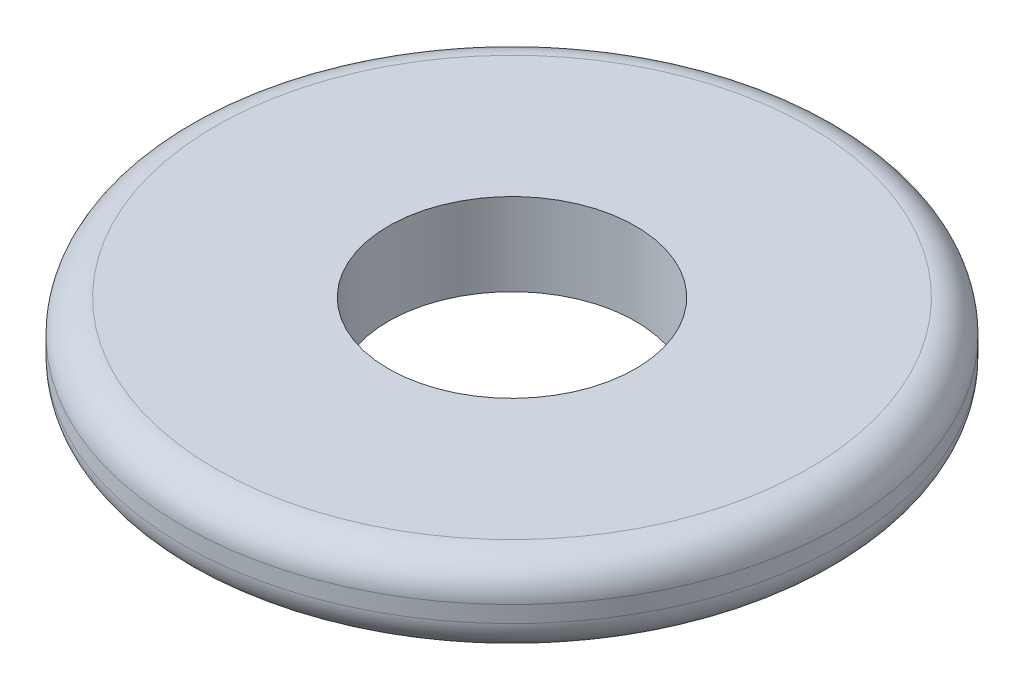
SolidWorks part; units mm, degrees
ref_plane "Front Plane" through (0, 0, 0) normal (0, 0, 1) x (1, 0, 0)
ref_plane "Top Plane" through (0, 0, 0) normal (0, 1, 0) x (1, 0, 0)
ref_plane "Right Plane" through (0, 0, 0) normal (1, 0, 0) x (0, 0, -1)
sketch "Sketch1" plane through (0, 0, 0) normal (0, 1, 0) x (1, 0, 0)
  circle A0 centre (0, 0) radius 25.4
  circle A2 centre (0, 0) radius 9.525
  dimension "D1" = 50.8
  dimension "D2" = 19.05
extrude "Boss-Extrude1" add sketch "Sketch1" along normal blind 6.35
fillet "Fillet1" radius 2.54 2 edges at (0, 0, 25.4) (0, 6.35, 25.4)
